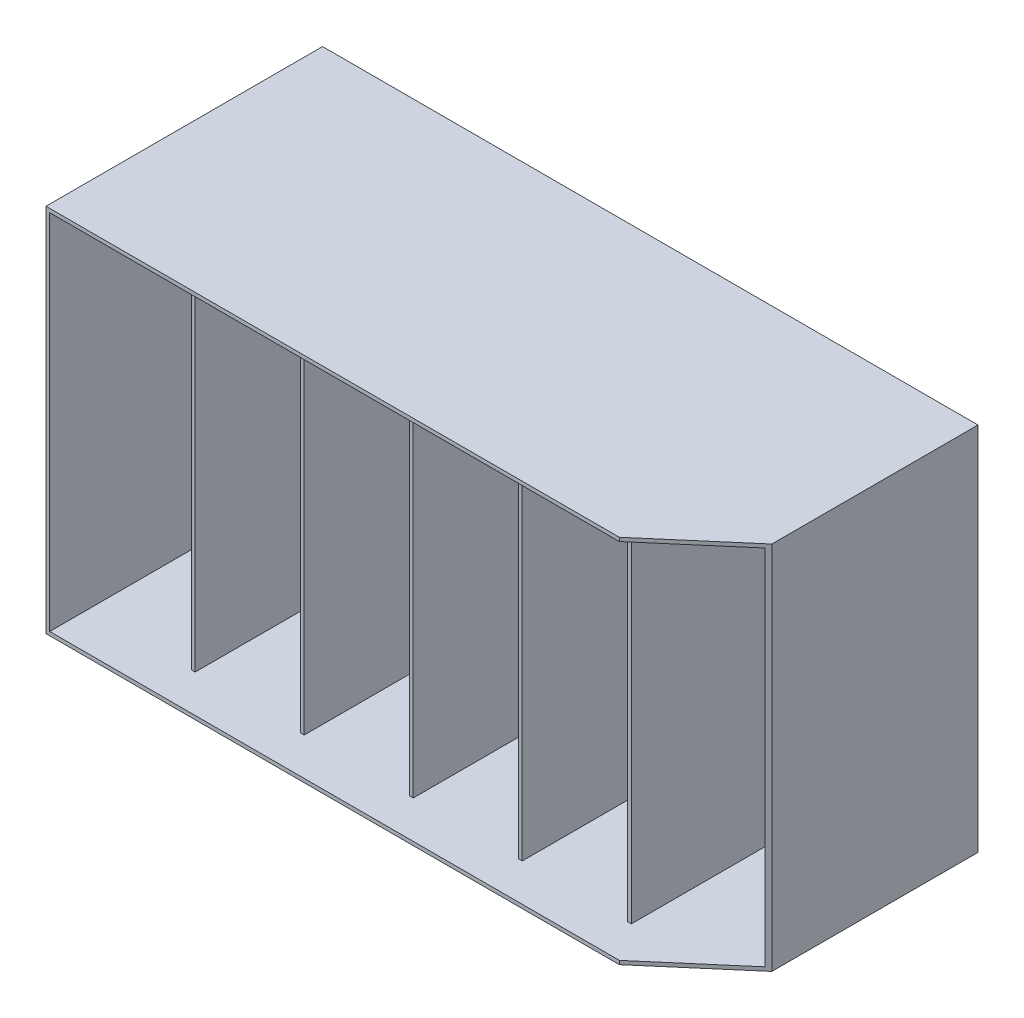
SolidWorks part; units mm, degrees
material "Custom Plastic"
ref_plane "X-Y Datum" through (0, 0, 0) normal (0, 0, 1) x (1, 0, 0)
ref_plane "X-Z Datum" through (0, 0, 0) normal (0, 1, 0) x (1, 0, 0)
ref_plane "Y-Z Datum" through (0, 0, 0) normal (1, 0, 0) x (0, 0, -1)
sketch "Sketch1" plane through (0, 0, 0) normal (0, 0, 1) x (1, 0, 0)
  line L0 (-276.225, 0) -> (276.225, 0) construction
  line L1 (-276.225, 154.6125) -> (276.225, 154.6125)
  line L2 (-276.225, 154.6125) -> (-276.225, -154.6125)
  line L3 (-276.225, -154.6125) -> (276.225, -154.6125)
  line L4 (276.225, 154.6125) -> (276.225, -154.6125)
  line L5 (-276.225, 154.6125) -> (276.225, -154.6125) construction
  line L6 (-276.225, -154.6125) -> (276.225, 154.6125) construction
  line L7 (-274.6375, 153.025) -> (-189.0375, 153.025) construction
  line L8 (-274.6375, 153.025) -> (-274.6375, -153.025) construction
  line L9 (-274.6375, -153.025) -> (-189.0375, -153.025) construction
  line L10 (-189.0375, 153.025) -> (-189.0375, -153.025) construction
  line L11 (-274.6375, 153.025) -> (-189.0375, -153.025) construction
  line L12 (-274.6375, -153.025) -> (-189.0375, 153.025) construction
  line L13 (-187.45, -154.6125) -> (-187.45, 154.6125)
  line L14 (-279.4, 157.7875) -> (279.4, 157.7875)
  line L15 (279.4, 157.7875) -> (279.4, -157.7875)
  line L16 (-279.4, -157.7875) -> (279.4, -157.7875)
  line L17 (-279.4, 157.7875) -> (-279.4, -157.7875)
  line L18 (-184.275, -154.6125) -> (-184.275, 154.6125)
  line L19 (-187.45, 0) -> (-184.275, 0) construction
  line L20 (-181.6735, 153.025) -> (-181.6735, -153.025) construction
  line L21 (-181.6735, 153.025) -> (-96.0735, 153.025) construction
  line L22 (-96.0735, 153.025) -> (-96.0735, -153.025) construction
  line L23 (-181.6735, -153.025) -> (-96.0735, -153.025) construction
  line L24 (-94.486, -154.6125) -> (-94.486, 154.6125)
  line L25 (-91.311, -154.6125) -> (-91.311, 154.6125)
  line L26 (-88.7095, 153.025) -> (-88.7095, -153.025) construction
  line L27 (-88.7095, 153.025) -> (-3.1095, 153.025) construction
  line L28 (-3.1095, 153.025) -> (-3.1095, -153.025) construction
  line L29 (-88.7095, -153.025) -> (-3.1095, -153.025) construction
  line L30 (-1.522, -154.6125) -> (-1.522, 154.6125)
  line L31 (1.653, -154.6125) -> (1.653, 154.6125)
  line L32 (4.2545, 153.025) -> (4.2545, -153.025) construction
  line L33 (4.2545, 153.025) -> (89.8545, 153.025) construction
  line L34 (89.8545, 153.025) -> (89.8545, -153.025) construction
  line L35 (4.2545, -153.025) -> (89.8545, -153.025) construction
  line L36 (91.442, -154.6125) -> (91.442, 154.6125)
  line L37 (94.617, -154.6125) -> (94.617, 154.6125)
  line L38 (97.2185, 153.025) -> (97.2185, -153.025) construction
  line L39 (97.2185, 153.025) -> (182.8185, 153.025) construction
  line L40 (182.8185, 153.025) -> (182.8185, -153.025) construction
  line L41 (97.2185, -153.025) -> (182.8185, -153.025) construction
  line L42 (184.406, -154.6125) -> (184.406, 154.6125)
  line L43 (187.581, -154.6125) -> (187.581, 154.6125)
  line L44 (-181.6735, -153.025) -> (-96.0735, 153.025) construction
  line L45 (-181.6735, 153.025) -> (-96.0735, -153.025) construction
  line L46 (-88.7095, -153.025) -> (-3.1095, 153.025) construction
  line L47 (-88.7095, 153.025) -> (-3.1095, -153.025) construction
  line L48 (4.2545, -153.025) -> (89.8545, 153.025) construction
  line L49 (4.2545, 153.025) -> (89.8545, -153.025) construction
  line L50 (97.2185, -153.025) -> (182.8185, 153.025) construction
  line L51 (97.2185, 153.025) -> (182.8185, -153.025) construction
  point P0 (0, 0)
  point P6 (-231.8375, 0)
  point P23 (-185.8625, 0)
  point P24 (-138.8735, 0)
  dimension "D1" = 306.05
  dimension "D2" = 85.6
  dimension "D3" = 1.5875
  dimension "D4" = 1.5875
  dimension "D5" = 1.5875
  dimension "D8" = 45.975
  dimension "D10" = 558.8
  dimension "D12" = 92.964
  dimension "D6" = 3.175
  dimension "D7" = 3.175
  dimension "D9" = 5
  dimension "D11" = 5
extrude "Boss-Extrude1" add sketch "Sketch1" along normal blind 3.175 contours L3 L13 L1 L2 | L3 L24 L1 L18 | L3 L18 L1 L13 | L14 L17 L16 L15 L1 L4 L3 L2 | L3 L30 L1 L25 | L3 L25 L1 L24 | L3 L36 L1 L31 | L3 L31 L1 L30 | L3 L42 L1 L37 | L3 L37 L1 L36 | L43 L3 L4 L1 | L3 L43 L1 L42 region at (-231.8375, 0, 0) region at (-185.8625, 0, 0) region at (-139.3805, 0, 0) region at (-92.8985, 0, 0) region at (-46.4165, 0, 0) region at (0.0655, 0, 0) region at (46.5475, 0, 0) region at (93.0295, 0, 0) region at (139.5115, 0, 0) region at (185.9935, 0, 0) region at (231.903, 0, 0) region at (0, 157.1457, 0)
sketch "Sketch2" plane through (0, 0, 3.175) normal (0, 0, 1) x (1, 0, 0)
  line L0 (-187.45, -154.6125) -> (-187.45, 154.6125) construction
  line L1 (-94.486, -154.6125) -> (-94.486, 154.6125) construction
  line L2 (-184.275, -154.6125) -> (-184.275, 154.6125) construction
  line L3 (91.442, -154.6125) -> (91.442, 154.6125) construction
  line L4 (276.225, 154.6125) -> (-276.225, 154.6125)
  line L5 (276.225, -154.6125) -> (276.225, 154.6125)
  line L6 (-276.225, -154.6125) -> (276.225, -154.6125)
  line L7 (-276.225, 154.6125) -> (-276.225, -154.6125)
  line L8 (276.225, 154.6125) -> (-276.225, 154.6125)
  line L9 (276.225, -154.6125) -> (276.225, 154.6125)
  line L10 (-276.225, -154.6125) -> (276.225, -154.6125)
  line L11 (-276.225, 154.6125) -> (-276.225, -154.6125)
  line L12 (-279.4, -157.7875) -> (279.4, -157.7875)
  line L13 (-279.4, 157.7875) -> (-279.4, -157.7875)
  line L14 (279.4, 157.7875) -> (-279.4, 157.7875)
  line L15 (279.4, -157.7875) -> (279.4, 157.7875)
  line L16 (-279.4, -157.7875) -> (279.4, -157.7875)
  line L17 (-279.4, 157.7875) -> (-279.4, -157.7875)
  line L18 (279.4, 157.7875) -> (-279.4, 157.7875)
  line L19 (279.4, -157.7875) -> (279.4, 157.7875)
  line L20 (1.653, -154.6125) -> (1.653, 154.6125) construction
  line L21 (-1.522, -154.6125) -> (-1.522, 154.6125) construction
  line L22 (-91.311, -154.6125) -> (-91.311, 154.6125) construction
  line L23 (187.581, -154.6125) -> (187.581, 154.6125) construction
  line L24 (184.406, -154.6125) -> (184.406, 154.6125) construction
  line L25 (94.617, -154.6125) -> (94.617, 154.6125) construction
  line L26 (-187.45, -154.6125) -> (-187.45, 154.6125)
  line L27 (-94.486, -154.6125) -> (-94.486, 154.6125)
  line L28 (-184.275, -154.6125) -> (-184.275, 154.6125)
  line L29 (91.442, -154.6125) -> (91.442, 154.6125)
  line L30 (1.653, -154.6125) -> (1.653, 154.6125)
  line L31 (-1.522, -154.6125) -> (-1.522, 154.6125)
  line L32 (-91.311, -154.6125) -> (-91.311, 154.6125)
  line L33 (187.581, -154.6125) -> (187.581, 154.6125)
  line L34 (184.406, -154.6125) -> (184.406, 154.6125)
  line L35 (94.617, -154.6125) -> (94.617, 154.6125)
  line M9 (279.4, 157.7875) -> (-279.4, 157.7875)
  line M10 (-279.4, 157.7875) -> (-279.4, -157.7875)
  line M11 (-279.4, -157.7875) -> (279.4, -157.7875)
  line M12 (279.4, -157.7875) -> (279.4, 157.7875)
  dimension "D1" = 0
  dimension "D2" = 0
extrude "Boss-Extrude2" add sketch "Sketch2" along normal blind 200.6 contours L11 L8 L9 L10 M12 M9 M10 M11 | L10 L28 L8 L26 | L10 L32 L8 L27 | L31 L10 L30 L8 | L10 L35 L8 L29 | L34 L10 L33 L8 region at (185.9935, 0, 3.175) region at (93.0295, 0, 3.175) region at (0.0655, 0, 3.175) region at (-92.8985, 0, 3.175) region at (-185.8625, 0, 3.175) region at (-278.7582, 0, 3.175)
sketch "Sketch3" plane through (0, 0, 203.775) normal (0, 0, 1) x (1, 0, 0)
  line L0 (-187.45, -154.6125) -> (-187.45, 154.6125) construction
  line L1 (-94.486, -154.6125) -> (-94.486, 154.6125) construction
  line L2 (-184.275, -154.6125) -> (-184.275, 154.6125) construction
  line L3 (91.442, -154.6125) -> (91.442, 154.6125) construction
  line L4 (276.225, 154.6125) -> (-276.225, 154.6125)
  line L5 (276.225, -154.6125) -> (276.225, 154.6125)
  line L6 (-276.225, -154.6125) -> (276.225, -154.6125)
  line L7 (-276.225, 154.6125) -> (-276.225, -154.6125)
  line L8 (276.225, 154.6125) -> (-276.225, 154.6125)
  line L9 (276.225, -154.6125) -> (276.225, 154.6125)
  line L10 (-276.225, -154.6125) -> (276.225, -154.6125)
  line L11 (-276.225, 154.6125) -> (-276.225, -154.6125)
  line L12 (-279.4, -157.7875) -> (279.4, -157.7875)
  line L13 (-279.4, 157.7875) -> (-279.4, -157.7875)
  line L14 (279.4, 157.7875) -> (-279.4, 157.7875)
  line L15 (279.4, -157.7875) -> (279.4, 157.7875)
  line L16 (-279.4, -157.7875) -> (279.4, -157.7875)
  line L17 (-279.4, 157.7875) -> (-279.4, -157.7875)
  line L18 (279.4, 157.7875) -> (-279.4, 157.7875)
  line L19 (279.4, -157.7875) -> (279.4, 157.7875)
  line L20 (1.653, -154.6125) -> (1.653, 154.6125) construction
  line L21 (-1.522, -154.6125) -> (-1.522, 154.6125) construction
  line L22 (-91.311, -154.6125) -> (-91.311, 154.6125) construction
  line L23 (187.581, -154.6125) -> (187.581, 154.6125) construction
  line L24 (184.406, -154.6125) -> (184.406, 154.6125) construction
  line L25 (94.617, -154.6125) -> (94.617, 154.6125) construction
  line L26 (-187.45, -154.6125) -> (-187.45, 154.6125)
  line L27 (-94.486, -154.6125) -> (-94.486, 154.6125)
  line L28 (-184.275, -154.6125) -> (-184.275, 154.6125)
  line L29 (91.442, -154.6125) -> (91.442, 154.6125)
  line L30 (1.653, -154.6125) -> (1.653, 154.6125)
  line L31 (-1.522, -154.6125) -> (-1.522, 154.6125)
  line L32 (-91.311, -154.6125) -> (-91.311, 154.6125)
  line L33 (187.581, -154.6125) -> (187.581, 154.6125)
  line L34 (184.406, -154.6125) -> (184.406, 154.6125)
  line L35 (94.617, -154.6125) -> (94.617, 154.6125)
  line M9 (94.617, 154.6125) -> (184.406, 154.6125)
  line M11 (184.406, -154.6125) -> (94.617, -154.6125)
  line M13 (1.653, 154.6125) -> (91.442, 154.6125)
  line M15 (91.442, -154.6125) -> (1.653, -154.6125)
  line M17 (-91.311, 154.6125) -> (-1.522, 154.6125)
  line M19 (-1.522, -154.6125) -> (-91.311, -154.6125)
  line M21 (-184.275, 154.6125) -> (-94.486, 154.6125)
  line M23 (-94.486, -154.6125) -> (-184.275, -154.6125)
  line M25 (-276.225, 154.6125) -> (-187.45, 154.6125)
  line M27 (-187.45, -154.6125) -> (-276.225, -154.6125)
  line M28 (-276.225, -154.6125) -> (-276.225, 154.6125)
  line M30 (187.581, 154.6125) -> (276.225, 154.6125)
  line M31 (276.225, 154.6125) -> (276.225, -154.6125)
  line M32 (276.225, -154.6125) -> (187.581, -154.6125)
  line M33 (279.4, -157.7875) -> (279.4, 157.7875)
  line M34 (279.4, 157.7875) -> (-279.4, 157.7875)
  line M35 (-279.4, 157.7875) -> (-279.4, -157.7875)
  line M36 (-279.4, -157.7875) -> (279.4, -157.7875)
  dimension "D1" = 0
  dimension "D2" = 0
extrude "Boss-Extrude3" add sketch "Sketch3" along normal blind 32 contours L10 L8 M36 M33 M34 M35 M27 M28 M25 M21 M17 M13 M9 M30 M31 M32 M11 M15 M19 M23 region at (-278.7582, 0, 203.775)
sketch "Sketch4" plane through (0, -157.7875, 0) normal (0, -1, 0) x (1, 0, 0)
  line L0 (209.4, 235.775) -> (279.4, 175.775)
  line L1 (-279.4, 235.775) -> (279.4, 235.775) construction
  line L2 (279.4, 235.775) -> (279.4, 0) construction
  line M3 (279.4, 0) -> (279.4, 235.775)
  line M4 (279.4, 235.775) -> (-279.4, 235.775)
  dimension "D1" = 60
  dimension "D2" = 70
extrude "Cut-Extrude1" cut sketch "Sketch4" against normal through all contours L0 M4 M3 region at (256.0667, -157.7875, 215.775)
sketch "Sketch5" plane through (187.581, 0, 0) normal (1, 0, 0) x (0, 0, -1)
  line L0 (-3.175, 0) -> (-117.475, 0)
  line L1 (-3.175, -154.6125) -> (-3.175, 154.6125) construction
  line L2 (-117.475, 154.6125) -> (-117.475, 0)
  line L3 (-203.775, 154.6125) -> (-3.175, 154.6125) construction
  line L4 (-117.475, -154.6125) -> (-117.475, 0)
  line L5 (-203.775, -154.6125) -> (-3.175, -154.6125) construction
  dimension "D1" = 114.3
